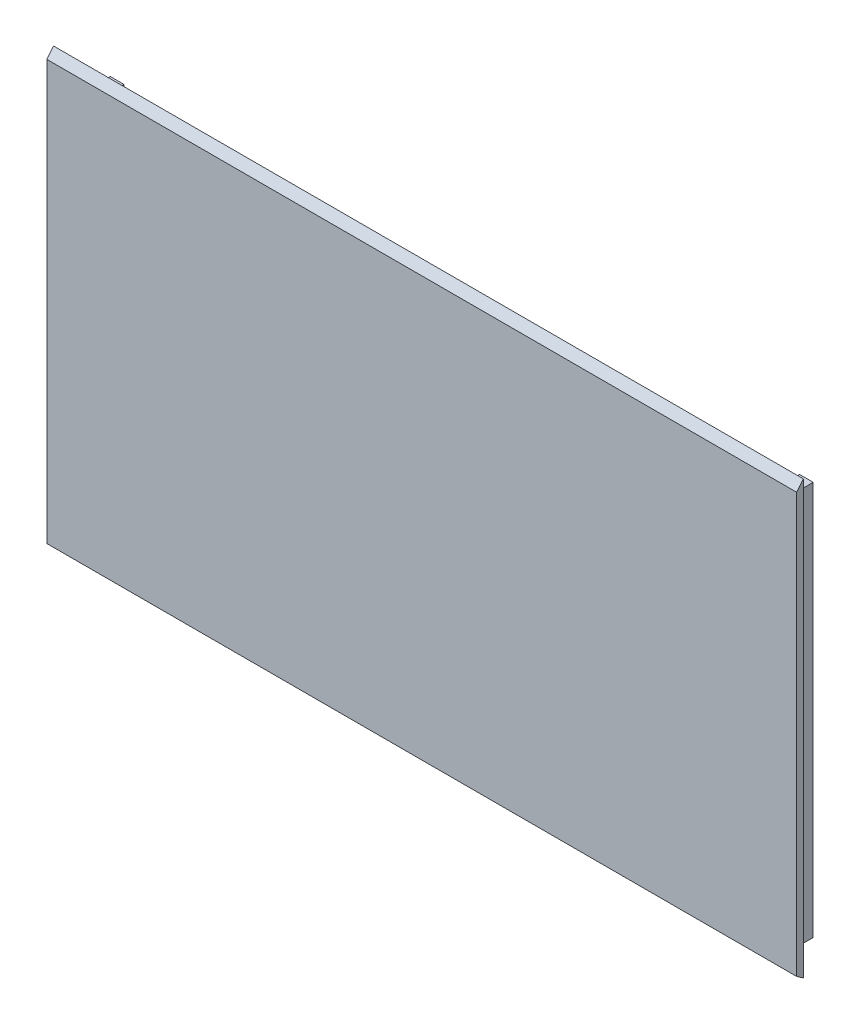
SolidWorks part; units mm, degrees
material "PLA"
ref_plane "Front Plane" through (0, 0, 0) normal (0, 0, 1) x (1, 0, 0)
ref_plane "Top Plane" through (0, 0, 0) normal (0, 1, 0) x (1, 0, 0)
ref_plane "Right Plane" through (0, 0, 0) normal (1, 0, 0) x (0, 0, -1)
sketch "Sketch2" plane through (0, 0, 0) normal (0, 0, 1) x (1, 0, 0)
  line L1 (-82.55, 47.585) -> (82.55, 47.585)
  line L2 (-82.55, 47.585) -> (-82.55, -47.585)
  line L3 (-82.55, -47.585) -> (82.55, -47.585)
  line L4 (82.55, 47.585) -> (82.55, -47.585)
  point P4 (0, 47.585)
  point P6 (-82.55, 0)
  dimension "D1" = 165.1
  dimension "D2" = 95.17
extrude "Boss-Extrude1" add sketch "Sketch2" along normal blind 1.5
sketch "Sketch3" plane through (0, 0, 0) normal (0, 0, -1) x (-1, 0, 0)
  line L12 (-82.55, 40.48) -> (82.55, 40.48) construction
  line L13 (-82.55, 40.48) -> (-82.55, -48.37) construction
  line L14 (-82.55, -48.37) -> (82.55, -48.37) construction
  line L15 (82.55, 40.48) -> (82.55, -48.37) construction
  line L16 (-77.46, 40.765) -> (-74.135, 40.765) construction
  line L17 (-77.46, 40.765) -> (-77.46, -46.345) construction
  line L18 (-77.46, -46.345) -> (-74.135, -46.345) construction
  line L19 (-74.135, 40.765) -> (-74.135, -46.345) construction
  line L20 (74.285, 40.765) -> (77.61, 40.765) construction
  line L21 (74.285, 40.765) -> (74.285, -46.345) construction
  line L22 (74.285, -46.345) -> (77.61, -46.345) construction
  line L23 (77.61, 40.765) -> (77.61, -46.345) construction
  line L24 (-74.285, 40.615) -> (-74.285, -46.195)
  line L25 (-77.31, -46.195) -> (-74.285, -46.195)
  line L26 (-77.31, 40.615) -> (-77.31, -46.195)
  line L27 (-77.31, 40.615) -> (-74.285, 40.615)
  line L28 (74.435, 40.615) -> (77.46, 40.615)
  line L29 (77.46, 40.615) -> (77.46, -46.195)
  line L30 (74.435, -46.195) -> (77.46, -46.195)
  line L31 (74.435, 40.615) -> (74.435, -46.195)
  line L32 (-82.55, 47.585) -> (82.55, 47.585) construction
  line L34 (82.55, -47.585) -> (-82.55, -47.585) construction
  dimension "D1" = 165.1
  dimension "D2" = 88.85
  dimension "D3" = 5.09
  dimension "D4" = 1.39
  dimension "D5" = 6.97
  dimension "D6" = 6.97
  dimension "D7" = 1.39
  dimension "D9" = 5.09
  dimension "D10" = 3.025
  dimension "D11" = 3.025
  dimension "D8" = 0.15
extrude "Boss-Extrude2" add sketch "Sketch3" along normal blind 7.4
chamfer "Chamfer2" distance 1.5 angle 35 1 edges at (0, -47.585, 1.5) first distance on face at (0, -47.585, 0.75)
chamfer "Chamfer3" distance 1.7876 angle 40 1 edges at (0, 47.585, 1.5) first distance on face at (0, 0.5252, 1.5)
